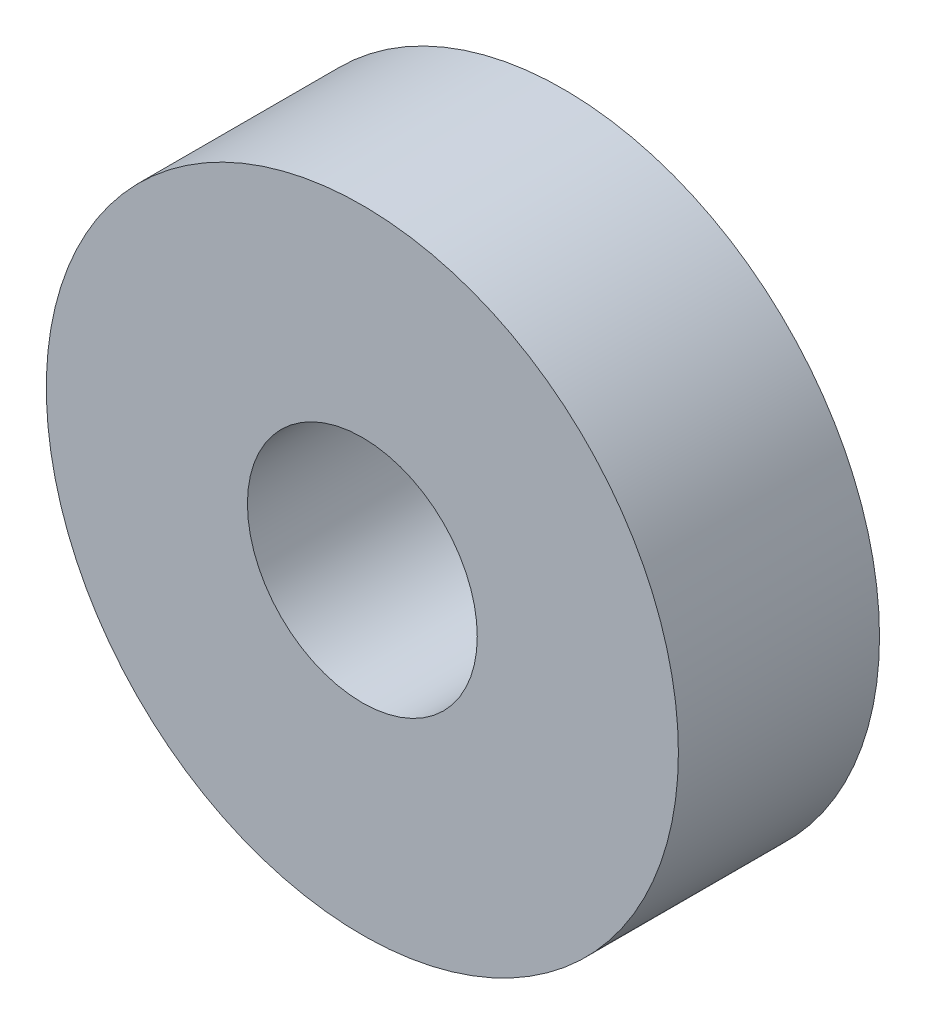
SolidWorks part; units mm, degrees
ref_plane "Front Plane" through (0, 0, 0) normal (0, 0, 1) x (1, 0, 0)
ref_plane "Top Plane" through (0, 0, 0) normal (0, 1, 0) x (1, 0, 0)
ref_plane "Right Plane" through (0, 0, 0) normal (1, 0, 0) x (0, 0, -1)
ref_axis "X" through (-88.99, 0, 0) along (1, 0, 0)
ref_axis "Y" through (0, 55, 0) along (0, -1, 0)
ref_axis "Z" through (0, 0, -88.99) along (0, 0, 1)
sketch "Sketch1" plane through (0, 0, 0) normal (0, 0, 1) x (1, 0, 0)
  circle A0 centre (0, 0) radius 4
  circle A1 centre (0, 0) radius 11
  dimension "D1" = 8
  dimension "D2" = 22
extrude "Boss-Extrude1" add sketch "Sketch1" along normal mid plane 7
